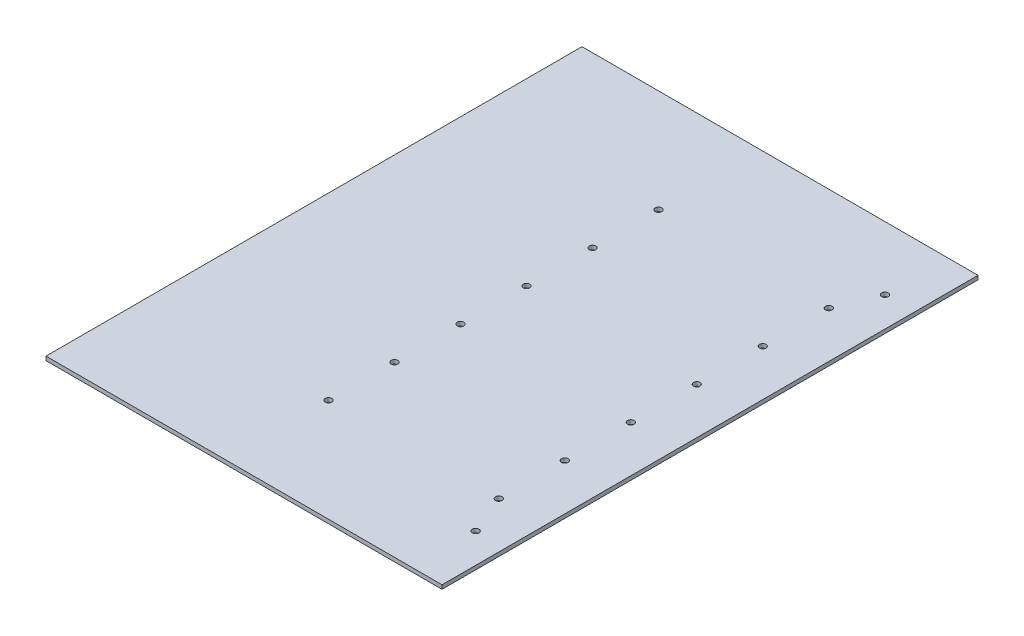
SolidWorks part; units mm, degrees
ref_plane "Front Plane" through (0, 0, 0) normal (0, 0, 1) x (1, 0, 0)
ref_plane "Top Plane" through (0, 0, 0) normal (0, 1, 0) x (1, 0, 0)
ref_plane "Right Plane" through (0, 0, 0) normal (1, 0, 0) x (0, 0, -1)
sketch "Sketch1" plane through (0, 0, 0) normal (0, 1, 0) x (1, 0, 0)
  line L1 (-150, -203) -> (150, -203)
  line L2 (-150, -203) -> (-150, 203)
  line L3 (-150, 203) -> (150, 203)
  line L4 (150, -203) -> (150, 203)
  line L5 (-150, -203) -> (150, 203) construction
  line L6 (-150, 203) -> (150, -203) construction
  point P0 (0, 0)
  dimension "D1" = 406
  dimension "D2" = 300
extrude "Boss-Extrude1" add sketch "Sketch1" along normal blind 3
sketch "Sketch2" plane through (0, 3, 0) normal (0, 1, 0) x (1, 0, 0)
  line L0 (0, -1000) -> (0, 49000) construction
  line L1 (115, -1000) -> (115, 49000) construction
  line L2 (150, -203) -> (150, 203) construction
  line L3 (150, 203) -> (-150, 203) construction
  line L6 (115, 125) -> (-14, 125) construction
  circle A0 centre (115, 125) radius 2.5
  circle A1 centre (115, 75) radius 2.5
  circle A2 centre (115, 25) radius 2.5
  circle A3 centre (115, -25) radius 2.5
  circle A4 centre (115, -75) radius 2.5
  circle A5 centre (115, -125) radius 2.5
  circle A12 centre (-14, 125) radius 2.5
  circle A13 centre (-14, 75) radius 2.5
  circle A14 centre (-14, 25) radius 2.5
  circle A15 centre (-14, -25) radius 2.5
  circle A16 centre (-14, -75) radius 2.5
  circle A17 centre (-14, -125) radius 2.5
  dimension "D2" = 78
  dimension "D3" = 5
  dimension "D5" = 50
  dimension "D6" = 2
  dimension "D1" = 35
  dimension "D7" = 129
  dimension "D4" = 6
extrude "Cut-Extrude1" cut sketch "Sketch2" against normal up to next
sketch "Sketch3" plane through (0, 3, 0) normal (0, 1, 0) x (1, 0, 0)
  line L0 (-1000, 0) -> (49000, 0) construction
  line L1 (-150, -203) -> (150, -203) construction
  line L2 (150, -203) -> (150, 203) construction
  circle A0 centre (127.5, -155) radius 2.5
  circle A1 centre (127.5, 155) radius 2.5
  dimension "D2" = 5
  dimension "D1" = 48
  dimension "D3" = 22.5
extrude "Cut-Extrude2" cut sketch "Sketch3" against normal through all
